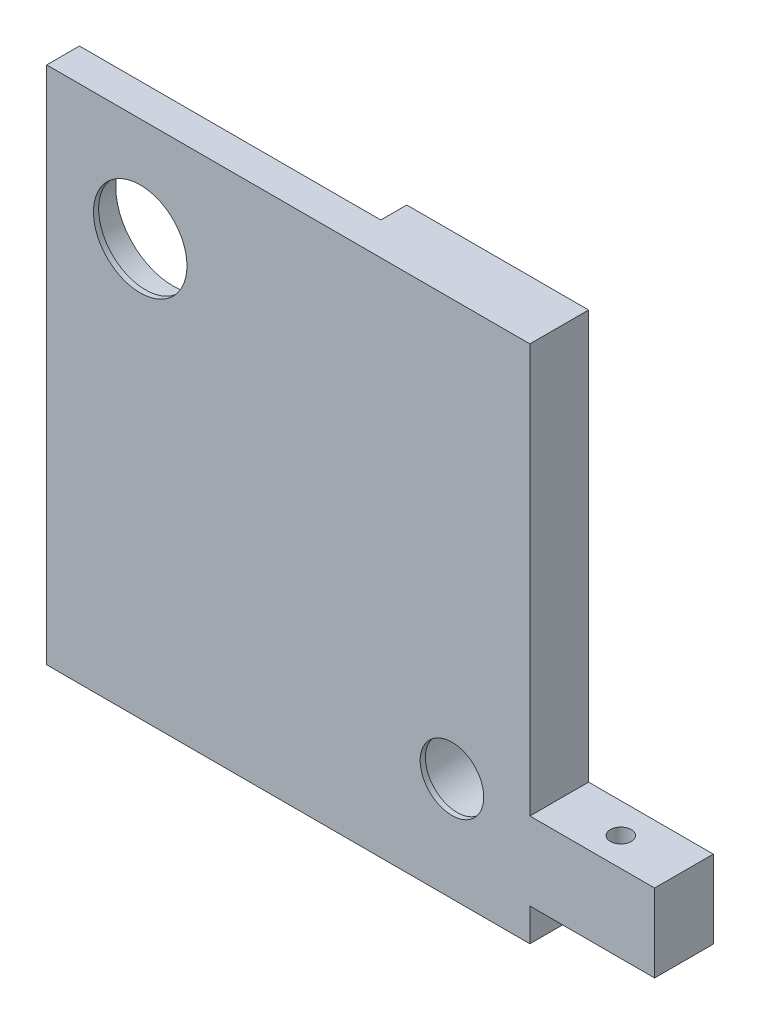
SolidWorks part; units mm, degrees
ref_plane "Front Plane" through (0, 0, 0) normal (0, 0, 1) x (1, 0, 0)
ref_plane "Top Plane" through (0, 0, 0) normal (0, 1, 0) x (1, 0, 0)
ref_plane "Right Plane" through (0, 0, 0) normal (1, 0, 0) x (0, 0, -1)
sketch "Sketch1" plane through (0, 0, 0) normal (0, 0, 1) x (1, 0, 0)
  line L1 (-76.1871, 64.9281) -> (16.8129, 64.9281)
  line L2 (-76.1871, 64.9281) -> (-76.1871, -35.0719)
  line L3 (-76.1871, -35.0719) -> (16.8129, -35.0719)
  line L4 (16.8129, 64.9281) -> (16.8129, -35.0719)
  dimension "D1" = 93
  dimension "D2" = 100
extrude "Boss-Extrude2" add sketch "Sketch1" along normal blind 6.3 contours L1 L4 L3 L2
sketch "Sketch3" plane through (0, 0, 0) normal (0, 0, -1) x (-1, 0, 0)
  line L0 (76.1871, -35.0719) -> (-16.8129, -35.0719) construction
  line L1 (-16.8129, 64.9281) -> (18.1871, 64.9281)
  line L2 (-16.8129, 64.9281) -> (-16.8129, -35.0719)
  line L3 (-16.8129, -35.0719) -> (18.1871, -35.0719)
  line L4 (18.1871, 64.9281) -> (18.1871, -35.0719)
  line L5 (-16.8129, 64.9281) -> (-16.8129, -35.0719) construction
  dimension "D1" = 0
  dimension "D2" = 0
  dimension "D3" = 35
  dimension "D4" = 100
extrude "Boss-Extrude3" add sketch "Sketch3" along normal blind 5
sketch "Sketch4" plane through (16.8129, 0, 0) normal (1, 0, 0) x (0, 0, -1)
  line L0 (-6.3, 64.9281) -> (-6.3, -35.0719) construction
  line L1 (-6.3, -13.7719) -> (5, -13.7719)
  line L2 (-6.3, -13.7719) -> (-6.3, -28.7719)
  line L3 (-6.3, -28.7719) -> (5, -28.7719)
  line L4 (5, -13.7719) -> (5, -28.7719)
  line L5 (5, 64.9281) -> (5, -35.0719) construction
  line L6 (-6.3, -35.0719) -> (5, -35.0719) construction
  dimension "D1" = 6.3
  dimension "D2" = 15
extrude "Boss-Extrude4" add sketch "Sketch4" along normal blind 24
sketch "Sketch5" plane through (0, -13.7719, 0) normal (0, 1, 0) x (1, 0, 0)
  line L0 (40.8129, -6.3) -> (16.8129, -6.3) construction
  line L2 (16.8129, 5) -> (16.8129, -6.3) construction
  circle A0 centre (28.8129, -0.8) radius 2
  dimension "D2" = 4
  dimension "D3" = 12
  dimension "D1" = 5.5
extrude "Cut-Extrude1" cut sketch "Sketch5" against normal blind 50
sketch "Sketch6" plane through (0, 0, -5) normal (0, 0, -1) x (-1, 0, 0)
  line L0 (-16.8129, -35.0719) -> (18.1871, -35.0719) construction
  line L1 (-16.8129, -28.7719) -> (-16.8129, -35.0719) construction
  circle A0 centre (-1.8129, -15.0719) radius 8.115
  dimension "D1" = 16.23
  dimension "D2" = 20
  dimension "D3" = 15
extrude "Cut-Extrude2" cut sketch "Sketch6" against normal blind 50
sketch "Sketch7" plane through (0, 0, 0) normal (0, 0, -1) x (-1, 0, 0)
  line L0 (76.1871, -35.0719) -> (18.1871, -35.0719) construction
  line L2 (-16.8129, 64.9281) -> (-16.8129, -13.7719) construction
  circle A0 centre (58.1871, 44.9281) radius 11
  dimension "D1" = 22
  dimension "D2" = 80
  dimension "D3" = 75
extrude "Cut-Extrude3" cut sketch "Sketch7" against normal blind 50
extrude "Extrude-Thin1" add sketch "Sketch7<2>" along normal blind 1 from surface thin starting at face at (-47.1871, 44.9281, 6.3) thin type one direction reverse wall 2
sketch "Sketch7<2>" plane through (0, 0, 0) normal (0, 0, -1) x (-1, 0, 0) same geometry as "Sketch7"
extrude "Extrude-Thin2" add sketch "Sketch6<2>" along normal blind 1 from surface thin starting at face at (9.9279, -15.0719, 6.3) thin type one direction reverse wall 2
sketch "Sketch6<2>" plane through (0, 0, -5) normal (0, 0, -1) x (-1, 0, 0) same geometry as "Sketch6"
